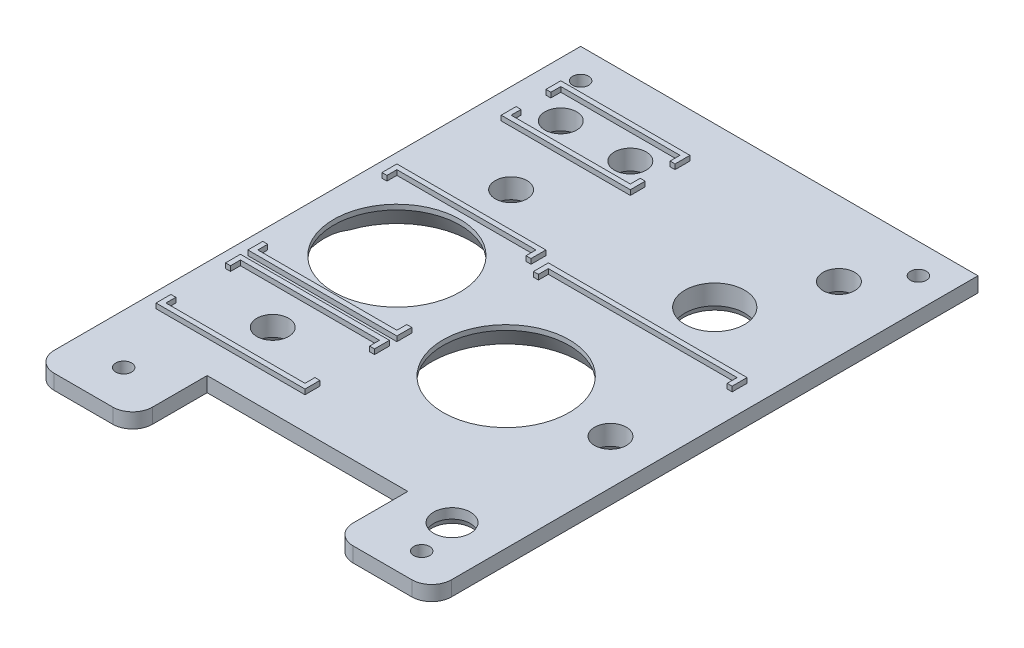
SolidWorks part; units mm, degrees
ref_plane "Спереди" through (0, 0, 0) normal (0, 0, 1) x (1, 0, 0)
ref_plane "Сверху" through (0, 0, 0) normal (0, 1, 0) x (1, 0, 0)
ref_plane "Справа" through (0, 0, 0) normal (1, 0, 0) x (0, 0, -1)
sketch "Sketch1" plane through (0, 0, 0) normal (0, 1, 0) x (1, 0, 0)
  line L1 (40, -55) -> (-40, -55)
  line L2 (40, -55) -> (40, 55)
  line L3 (40, 55) -> (-40, 55)
  line L4 (-40, -55) -> (-40, 55)
  line L5 (40, -55) -> (-40, 55) construction
  line L6 (40, 55) -> (-40, -55) construction
  point P0 (0, 0)
  dimension "D1" = 80
  dimension "D2" = 110
extrude "Boss-Extrude1" add sketch "Sketch1" along normal blind 3
sketch "Sketch2" plane through (0, 0, 55) normal (0, 0, 1) x (1, 0, 0)
  line L0 (0, 3) -> (0, 0) construction
  line L1 (-40, 3) -> (40, 3) construction
  line L2 (-40, 0) -> (40, 0) construction
  line L4 (20.2, 0) -> (-20.2, 0)
  line L5 (20.2, 0) -> (20.2, 3)
  line L6 (20.2, 3) -> (-20.2, 3)
  line L7 (-20.2, 0) -> (-20.2, 3)
  line L8 (20.2, 0) -> (-20.2, 3) construction
  line L9 (20.2, 3) -> (-20.2, 0) construction
  point P6 (0, 1.5)
  dimension "D1" = 40.4
extrude "Cut-Extrude1" cut sketch "Sketch2" against normal blind 15
fillet "Fillet1" radius 4 4 edges at (20.2, 1.5, 55) (40, 1.5, 55) (-20.2, 1.5, 55) (-40, 1.5, 55)
sketch "Sketch7" plane through (0, 0, 0) normal (0, -1, 0) x (1, 0, 0)
  line L0 (-40, -55) -> (-40, 51) construction
  line L1 (40, -55) -> (-40, -55) construction
  line L2 (36.8, 34.8) -> (-36.8, 34.8)
  line L3 (36.8, 34.8) -> (36.8, -51.8)
  line L4 (36.8, -51.8) -> (-36.8, -51.8)
  line L5 (-36.8, 34.8) -> (-36.8, -51.8)
  line L6 (36.8, 34.8) -> (-36.8, -51.8) construction
  line L7 (40, 51) -> (40, -55) construction
  line L8 (36.8, -51.8) -> (-36.8, 34.8) construction
  point P0 (0, -8.5)
  point P11 (0, 34.8)
  point P12 (0, -55)
  dimension "D1" = 3.2
  dimension "D2" = 3.2
  dimension "D3" = 3.2
  dimension "D4" = 89.8
extrude "Boss-Extrude2" add sketch "Sketch7" along normal blind 2
sketch "Sketch3" plane through (0, 3, 0) normal (0, 1, 0) x (1, 0, 0)
  line L0 (-40, 0) -> (40, 0) construction
  line L1 (-40, 55) -> (-40, -51) construction
  line L2 (40, -51) -> (40, 55) construction
  line L3 (-40, -10) -> (40, -10) construction
  line L4 (20.2, -40) -> (-20.2, -40) construction
  circle A0 centre (-22, 0) radius 12.7
  circle A1 centre (10, -10) radius 12.7
  point P10 (0, -10)
  point P13 (0, -40)
  point P16 (0, 0)
  dimension "D1" = 25.4
  dimension "D2" = 30
  dimension "D3" = 40
  dimension "D4" = 18
  dimension "D5" = 30
extrude "Cut-Extrude2" cut sketch "Sketch3" against normal through all
sketch "Sketch4" plane through (0, 3, 0) normal (0, 1, 0) x (1, 0, 0)
  line L0 (40, -51) -> (40, 55) construction
  line L1 (40, 55) -> (-40, 55) construction
  line L2 (19, 55) -> (19, -40) construction
  line L3 (40, -40) -> (-40, -40) construction
  line L4 (-40, 55) -> (-40, -51) construction
  line L5 (20.2, -40) -> (-20.2, -40) construction
  line L6 (40, 23) -> (-40, 23) construction
  line L7 (-22, 0) -> (-22, 55) construction
  line L8 (10, -10) -> (40, -10) construction
  line L9 (20.2, -41) -> (40, -41) construction
  line L10 (20.2, -40) -> (20.2, -51) construction
  line L11 (24.2, -55) -> (36, -55) construction
  line L12 (40, 40) -> (-40, 40) construction
  line L13 (-40, -25) -> (40, -25) construction
  line L15 (-22, 0) -> (-22, -54.3407) construction
  line L16 (-36, -55) -> (-24.2, -55) construction
  line L17 (-40, 49) -> (40, 49) construction
  line L18 (32, -41) -> (32, -55) construction
  line L19 (24.2, -55) -> (36, -55) construction
  circle A0 centre (19, 23) radius 6
  circle A1 centre (-22, 23) radius 3.2
  circle A2 centre (31, -10) radius 3.2
  circle A3 centre (30.1, -41) radius 3.7
  circle A4 centre (-29, 40) radius 3.2
  circle A5 centre (-15, 40) radius 3.2
  circle A6 centre (27, 40) radius 3.2
  circle A7 centre (-22, -25) radius 3.2
  arc A8 (-24.2, -55) -> (-20.2, -51) centre (-24.2, -51) ccw construction
  circle A9 centre (-30, -47) radius 1.6
  circle A10 centre (-34, 49) radius 1.6
  circle A11 centre (34, 49) radius 1.6
  circle A12 centre (32, -49) radius 1.6
  point P12 (0, -40)
  point P61 (0, 49)
  dimension "D1" = 12
  dimension "D7" = 7.4
  dimension "D8" = 14
  dimension "D14" = 6.4
  dimension "D17" = 3.2
  dimension "D20" = 3.2
  dimension "D25" = 3.2
  dimension "D27" = 13
  dimension "D2" = 21
  dimension "D3" = 32
  dimension "D6" = 9
  dimension "D12" = 14
  dimension "D13" = 7
  dimension "D15" = 30
  dimension "D16" = 15
  dimension "D18" = 10
  dimension "D19" = 8
  dimension "D21" = 68
  dimension "D22" = 34
  dimension "D23" = 6
  dimension "D24" = 8
  dimension "D26" = 6
extrude "Cut-Extrude3" cut sketch "Sketch4" against normal through all
chamfer "Chamfer2" distance 1.5 angle 20 4 edges at (36.8, -2, -8.5) (0, -2, -51.8) (-36.8, -2, -8.5) (0, -2, 34.8) first distance on face at (36.8, -1, -8.5) first distance on face at (0, -1, -51.8) first distance on face at (-36.8, -1, -8.5) first distance on face at (0, -1, 34.8)
chamfer "Chamfer3" distance 4 angle 30 2 edges at (-22, -2, 12.7) (10, -2, 22.7) first distance on face at (-22, -2, 12.7) first distance on face at (10, -2, 22.7)
sketch "Sketch8" plane through (0, 3, 0) normal (0, 1, 0) x (1, 0, 0)
  line L0 (-35, 43) -> (-35, 46)
  line L1 (-35, 46) -> (-9, 46)
  line L2 (-9, 46) -> (-9, 43)
  line L3 (-9, 43) -> (-10, 43)
  line L4 (-10, 43) -> (-10, 45)
  line L5 (-10, 45) -> (-34, 45)
  line L6 (-34, 45) -> (-34, 43)
  line L7 (-34, 43) -> (-35, 43)
  line L8 (-29, 40) -> (-15, 40) construction
  line L9 (31, -10) -> (10, -10) construction
  line L10 (10, -22.7) -> (10, 2.7) construction
  line L11 (-22, 45) -> (-22, 35) construction
  line L12 (-9, 37) -> (-9, 34)
  line L13 (-9, 34) -> (-35, 34)
  line L14 (-35, 34) -> (-35, 37)
  line L15 (-35, 37) -> (-34, 37)
  line L16 (-34, 37) -> (-34, 35)
  line L17 (-34, 35) -> (-10, 35)
  line L18 (-10, 35) -> (-10, 37)
  line L19 (-10, 37) -> (-9, 37)
  line L20 (-37, 12) -> (-37, 15)
  line L21 (-37, 15) -> (-7, 15)
  line L22 (-7, 15) -> (-7, 12)
  line L23 (-7, 12) -> (-8, 12)
  line L24 (-8, 12) -> (-8, 14)
  line L25 (-8, 14) -> (-36, 14)
  line L26 (-36, 14) -> (-36, 12)
  line L27 (-36, 12) -> (-37, 12)
  line L28 (-4.5, 10) -> (-4.5, 13)
  line L29 (-22, 14) -> (-22, -14) construction
  line L30 (-7, -12) -> (-7, -15)
  line L31 (-7, -15) -> (-37, -15)
  line L32 (-37, -15) -> (-37, -12)
  line L33 (-37, -12) -> (-36, -12)
  line L34 (-36, -12) -> (-36, -14)
  line L35 (-36, -14) -> (-8, -14)
  line L36 (-8, -14) -> (-8, -12)
  line L37 (-8, -12) -> (-7, -12)
  line L38 (-22, 12.7) -> (-22, -12.7) construction
  line L39 (-4.5, 13) -> (35.5, 13)
  line L40 (35.5, 13) -> (35.5, 10)
  line L41 (35.5, 10) -> (34.5, 10)
  line L42 (34.5, 10) -> (34.5, 12)
  line L43 (34.5, 12) -> (-3.5, 12)
  line L44 (-3.5, 12) -> (-3.5, 10)
  line L45 (-3.5, 10) -> (-4.5, 10)
  line L46 (15.5, 12) -> (15.5, -10) construction
  line L47 (-37, -19.5) -> (-37, -16.5)
  line L48 (-37, -16.5) -> (-7, -16.5)
  line L49 (-7, -16.5) -> (-7, -19.5)
  line L50 (-7, -19.5) -> (-8, -19.5)
  line L51 (-8, -19.5) -> (-8, -17.5)
  line L52 (-8, -17.5) -> (-36, -17.5)
  line L53 (-36, -17.5) -> (-36, -19.5)
  line L54 (-36, -19.5) -> (-37, -19.5)
  line L55 (-22, -17.5) -> (-22, -32.5) construction
  line L56 (-7, -30.5) -> (-7, -33.5)
  line L57 (-7, -33.5) -> (-37, -33.5)
  line L58 (-37, -33.5) -> (-37, -30.5)
  line L59 (-37, -30.5) -> (-36, -30.5)
  line L60 (-36, -30.5) -> (-36, -32.5)
  line L61 (-36, -32.5) -> (-8, -32.5)
  line L62 (-8, -32.5) -> (-8, -30.5)
  line L63 (-8, -30.5) -> (-7, -30.5)
  line L64 (-78.7082, -66.728) -> (-78.7082, -92.128) construction
  line L65 (-18.8, -25) -> (-25.2, -25) construction
  circle A1 centre (-22, 0) radius 12.7 construction
  circle A2 centre (10, -10) radius 12.7 construction
  circle A3 centre (-22, -25) radius 3.2 construction
  point P12 (-22, 40)
  point P15 (-22, 35)
  point P39 (-22, -14)
  point P51 (-22, 0)
  point P64 (-22, 0)
  point P66 (20.5, -10)
  point P81 (-22, -32.5)
  point P95 (-22, -25)
  point P96 (-22, -25)
  dimension "D1" = 1
  dimension "D2" = 1
  dimension "D3" = 26
  dimension "D4" = 3
  dimension "D5" = 10
  dimension "D6" = 30
  dimension "D7" = 28
  dimension "D8" = 40
  dimension "D9" = 5
  dimension "D10" = 22
  dimension "D11" = 15
  dimension "D12" = 1
  dimension "D13" = 1
extrude "Boss-Extrude3" add sketch "Sketch8" along normal blind 1
chamfer "Chamfer4" distance 1 angle 20 8 edges at (30.1, 0, 44.7) (31, -2, 13.2) (-22, -2, 28.2) (-22, -2, -19.8) (-29, -2, -36.8) (-15, -2, -36.8) (19, -2, -17) (27, -2, -36.8) first distance on face at (30.1, 3, 44.7) first distance on face at (31, -2, 13.2) first distance on face at (-22, -2, 28.2) first distance on face at (-22, -2, -19.8) first distance on face at (-29, -2, -36.8) first distance on face at (-15, -2, -36.8) first distance on face at (19, -2, -17) first distance on face at (27, -2, -36.8)
